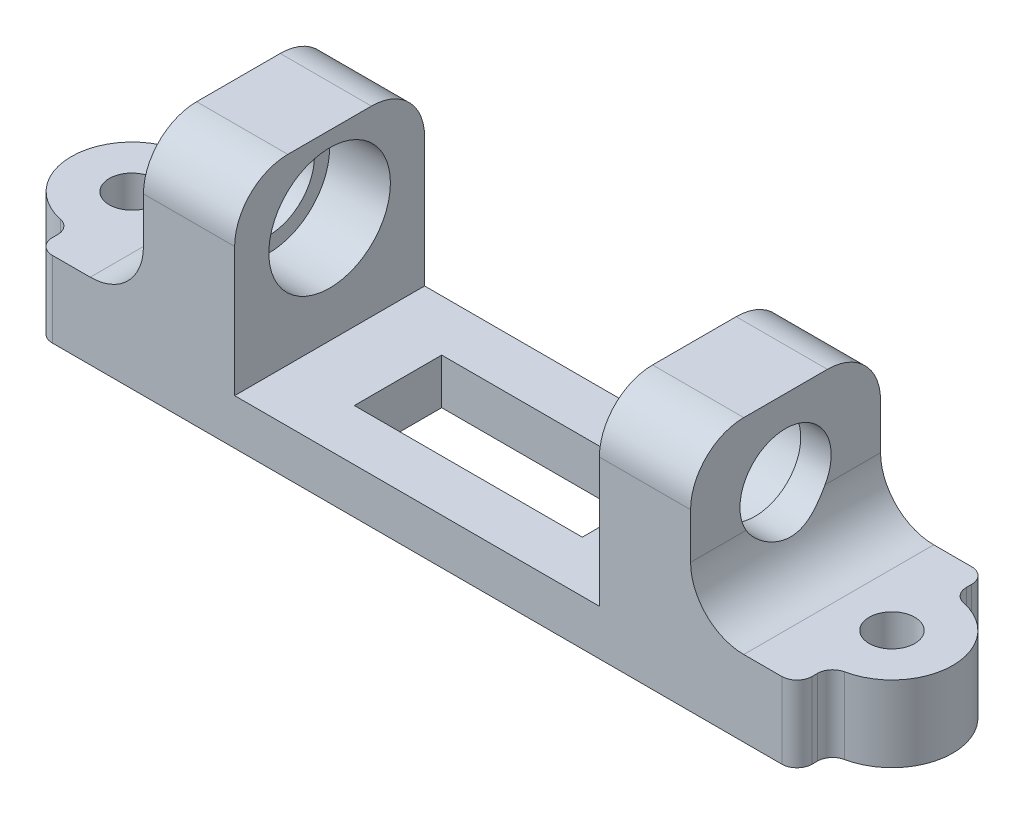
SolidWorks part; units mm, degrees
ref_plane "Front Plane" through (0, 0, 0) normal (0, 0, 1) x (1, 0, 0)
ref_plane "Top Plane" through (0, 0, 0) normal (0, 1, 0) x (1, 0, 0)
ref_plane "Right Plane" through (0, 0, 0) normal (1, 0, 0) x (0, 0, -1)
sketch "Sketch1" plane through (0, 0, 0) normal (0, 1, 0) x (1, 0, 0)
  line L0 (-25, -6.25) -> (-25, 6.25)
  line L1 (-25, -6.25) -> (25, -6.25)
  line L2 (-25, 6.25) -> (25, 6.25)
  line L3 (25, -6.25) -> (25, 6.25)
  line L4 (-25, -6.25) -> (25, 6.25) construction
  line L5 (-25, 6.25) -> (25, -6.25) construction
  circle A0 centre (-25, 0) radius 1.5
  circle A1 centre (25, 0) radius 1.5
  circle A2 centre (-25, 0) radius 4
  circle A3 centre (25, 0) radius 4
  point P1 (0, 0)
  dimension "D3" = 3
  dimension "D4" = 3
  dimension "D5" = 8
  dimension "D6" = 8
  dimension "D1" = 50
  dimension "D2" = 12.5
extrude "Boss-Extrude1" add sketch "Sketch1" along normal blind 5 contours A3 L3 L2 L0 A2 L1 | L0 A2 A0 | L0 A2 A0 | L3 A3 A1 | L3 A3 A1 region at (0, 0, 0) region at (-26.8713, 0, 0) region at (-23.1287, 0, 0) region at (23.1287, 0, 0) region at (26.8713, 0, 0)
sketch "Sketch2" plane through (0, 5, 0) normal (0, 1, 0) x (1, 0, 0)
  line L0 (-25, 1.5) -> (-25, -1.5)
  line L1 (-25, 0) -> (-15, 0)
  line L2 (-18, -6.25) -> (-18, 6.25)
  line L3 (-18, -6.25) -> (-12, -6.25)
  line L4 (-18, 6.25) -> (-12, 6.25)
  line L5 (-12, -6.25) -> (-12, 6.25)
  line L6 (-18, -6.25) -> (-12, 6.25) construction
  line L7 (-18, 6.25) -> (-12, -6.25) construction
  circle A0 centre (-25, 0) radius 1.5 construction
  dimension "D1" = 10
  dimension "D2" = 6
  dimension "D3" = 12.5
extrude "Boss-Extrude2" add sketch "Sketch2" along normal blind 10 contours L3 L5 L4 L2 region at (-17.8613, 5, 3.125)
sketch "Sketch3" plane through (-12, 0, 0) normal (1, 0, 0) x (0, 0, -1)
  line L0 (0, 15) -> (0, 5)
  line L1 (-6.25, 15) -> (6.25, 15) construction
  line L2 (-6.25, 5) -> (6.25, 5) construction
  circle A0 centre (0, 10) radius 4
  circle A1 centre (0, 10) radius 3
  dimension "D1" = 8
  dimension "D2" = 6
extrude "Cut-Extrude1" cut sketch "Sketch3" against normal blind 4 contours A0
extrude "Cut-Extrude2" cut sketch "Sketch3<3>" against normal through all contours A1
sketch "Sketch3<3>" plane through (-12, 0, 0) normal (1, 0, 0) x (0, 0, -1) same geometry as "Sketch3"
fillet "Fillet6" radius 3.5 1 edges at (-18, 5, 0) type face fillet first side face at (-18, 10, 3) second side face at (-25, 5, 1.5)
fillet "Fillet7" radius 3.5 1 edges at (-15, 15, -6.25) type face fillet first side face at (-8.975, 6.4195, -6.25) second side face at (-15, 15, 0)
fillet "Fillet8" radius 3.5 1 edges at (-15, 15, 6.25) type face fillet first side face at (-8.975, 6.4195, 6.25) second side face at (-15, 15, 1.75)
mirror "Mirror4" about plane through (0, 0, 0) normal (1, 0, 0) of "Cut-Extrude2", "Cut-Extrude1", "Boss-Extrude2"
fillet "Fillet9" radius 3.5 1 edges at (15, 15, -6.25) type face fillet first side face at (15, 15, 0) second side face at (-1.5981, 6.9827, -6.25)
fillet "Fillet10" radius 3.5 1 edges at (15, 15, 6.25) type face fillet first side face at (-1.5981, 6.9827, 6.25) second side face at (15, 15, 1.75)
fillet "Fillet11" radius 3.5 1 edges at (18, 5, 0) type face fillet first side face at (18, 10, 3) second side face at (25, 5, 1.5)
fillet "Fillet12" radius 1 1 edges at (25, 2.5, -6.25) type face fillet first side face at (25, 2.5, -5.125) second side face at (0, 6.5393, -6.25)
fillet "Fillet13" radius 1 1 edges at (25, 2.5, 6.25) type face fillet first side face at (25, 2.5, 5.125) second side face at (0, 6.5393, 6.25)
fillet "Fillet14" radius 1 1 edges at (-25, 2.5, 6.25) type face fillet first side face at (-0.1429, 6.5393, 6.25) second side face at (-25, 2.5, 5.125)
fillet "Fillet15" radius 1 1 edges at (-25, 2.5, -6.25) type face fillet first side face at (-25, 2.5, -5.125) second side face at (-0.1429, 6.5393, -6.25)
fillet "Fillet16" radius 1 1 edges at (-25, 2.5, -4) type face fillet first side face at (-25, 2.5, -4.625) second side face at (-27, 2.5, 0)
fillet "Fillet17" radius 1 1 edges at (-25, 2.5, 4) type face fillet first side face at (-27.1899, 2.5, 0.2212) second side face at (-25, 2.5, 4.625)
fillet "Fillet18" radius 1 1 edges at (25, 2.5, 4) type face fillet first side face at (27, 2.5, 0) second side face at (25, 2.5, 4.625)
fillet "Fillet19" radius 1 1 edges at (25, 2.5, -4) type face fillet first side face at (25, 2.5, -4.625) second side face at (27.1899, 2.5, -0.2212)
sketch "Sketch4" plane through (0, 5, 0) normal (0, 1, 0) x (1, 0, 0)
  line L0 (-7.5, -2.875) -> (7.5, -2.875)
  line L1 (-7.5, -2.875) -> (-7.5, 2.875)
  line L2 (7.5, -2.875) -> (7.5, 2.875)
  line L3 (-7.5, 2.875) -> (7.5, 2.875)
  line L4 (-7.5, -2.875) -> (7.5, 2.875) construction
  line L5 (7.5, -2.875) -> (-7.5, 2.875) construction
  point P1 (0, 0)
  dimension "D1" = 15
  dimension "D2" = 5.75
extrude "Cut-Extrude3" cut sketch "Sketch4" against normal through all contours L0 L1 L3 L2
sketch "Sketch5" plane through (0, 5, 0) normal (0, 1, 0) x (1, 0, 0)
  line L1 (-12, 6.25) -> (12, 6.25)
  line L2 (-12, 6.25) -> (-12, -6.25)
  line L3 (-12, -6.25) -> (12, -6.25)
  line L4 (12, 6.25) -> (12, -6.25)
  line L5 (7.5, -2.875) -> (-7.5, -2.875)
  line L6 (7.5, -2.875) -> (7.5, 2.875)
  line L7 (7.5, 2.875) -> (-7.5, 2.875)
  line L8 (-7.5, -2.875) -> (-7.5, 2.875)
extrude "Cut-Extrude4" cut sketch "Sketch5" against normal blind 2
